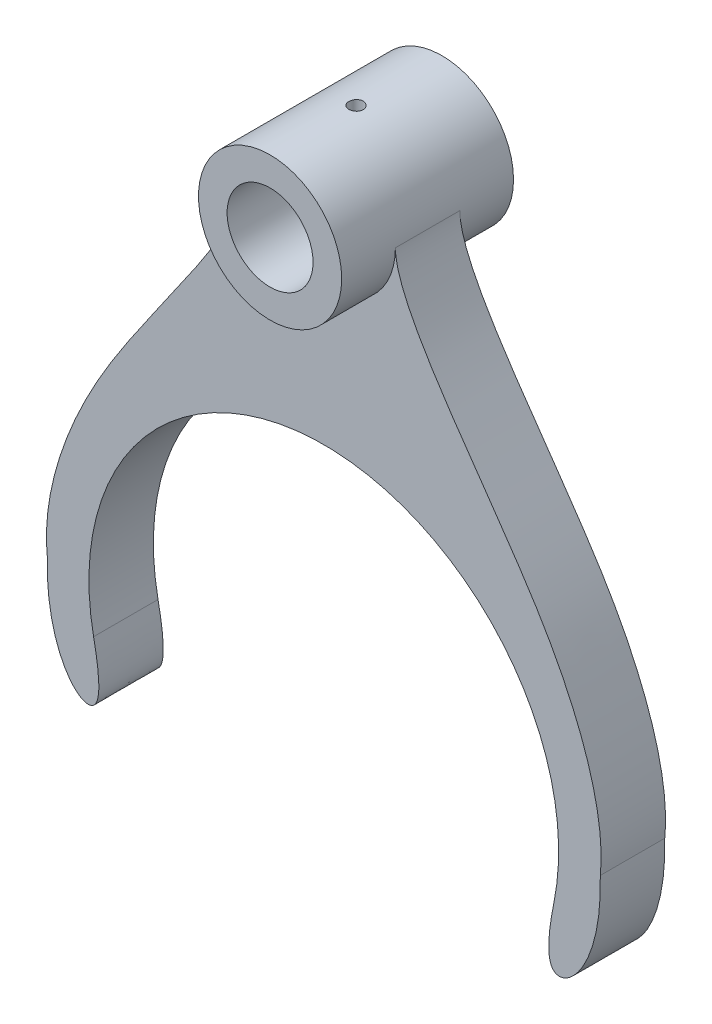
SolidWorks part; units mm, degrees
ref_plane "Front Plane" through (0, 0, 0) normal (0, 0, 1) x (1, 0, 0)
ref_plane "Top Plane" through (0, 0, 0) normal (0, 1, 0) x (1, 0, 0)
ref_plane "Right Plane" through (0, 0, 0) normal (1, 0, 0) x (0, 0, -1)
other "Default"
sketch "Sketch1" plane through (0, 0, 0) normal (0, 0, 1) x (1, 0, 0)
  line L1 (0, 0) -> (0, 200.3122) construction
  arc A0 (80.3693, -16.2717) -> (-80.3693, -16.2717) centre (0, 0) ccw
  circle A2 centre (0, 154) radius 25
  circle A3 centre (0, 154) radius 15
  spline S0 degree 3 poles (-96.5397, 0) (-96.4933, 1.7302) (-104.3462, 42.2229) (-25, 135.6296) (-25, 154) knots 0 0 0 0 0.598566 1 1 1 1
  spline S1 degree 3 poles (96.5397, 0) (96.4933, 1.7302) (104.3462, 42.2229) (25, 135.6296) (25, 154) knots 0 0 0 0 0.598566 1 1 1 1
  spline S2 degree 3 poles (-96.5397, 0) (-97.3266, -29.3315) (-77.4735, -47.5739) (-78.1125, -27.4188) (-80.3693, -16.2717) knots 0 0 0 0 0.663724 1 1 1 1
  spline S3 degree 3 poles (96.5397, 0) (97.3266, -29.3315) (77.4735, -47.5739) (78.1125, -27.4188) (80.3693, -16.2717) knots 0 0 0 0 0.663724 1 1 1 1
  dimension "D1" = 164
  dimension "D2" = 50
  dimension "D3" = 30
  dimension "D4" = 154
extrude "Boss-Extrude1" add sketch "Sketch1" along normal mid plane 22.5 contours A0 L1 A2 S0 S2 | L1 A0 S3 S1 A2 region at (-48.3479, 72.2921, 0) region at (48.3482, 72.2963, 0)
extrude "Boss-Extrude2" add sketch "Sketch1<3>" along normal mid plane 60 contours A2 L1 A3 | L1 A2 A3 region at (-17.2824, 136.7176, 0) region at (0.559, 134, 0)
sketch "Sketch1<3>" plane through (0, 0, 0) normal (0, 0, 1) x (1, 0, 0) same geometry as "Sketch1"
ref_plane "Plane1" through (0, 180, 0) normal (0, 1, 0) x (1, 0, 0)
sketch "Sketch3" plane through (0, 180, 0) normal (0, 1, 0) x (1, 0, 0)
  circle A0 centre (0, 0) radius 2.5
  dimension "D1" = 5
extrude "Cut-Extrude1" cut sketch "Sketch3" along normal through all from offset 30 offset against normal yes
